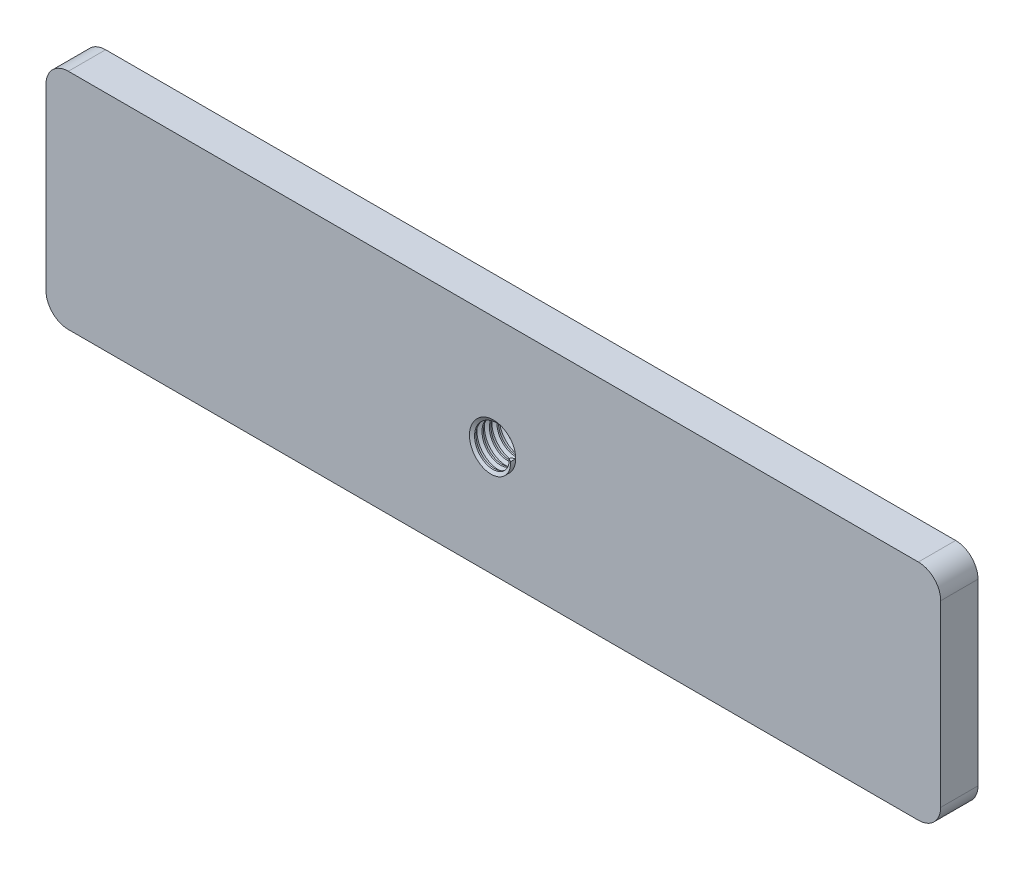
SolidWorks part; units mm, degrees
ref_plane "Front Plane" through (0, 0, 0) normal (0, 0, 1) x (1, 0, 0)
ref_plane "Top Plane" through (0, 0, 0) normal (0, 1, 0) x (1, 0, 0)
ref_plane "Right Plane" through (0, 0, 0) normal (1, 0, 0) x (0, 0, -1)
sketch "Sketch2" plane through (0, 0, 0) normal (0, 0, 1) x (1, 0, 0)
  line L1 (-57, -15) -> (57, -15)
  line L2 (-60, -12) -> (-60, 12)
  line L3 (-57, 15) -> (57, 15)
  line L4 (60, -12) -> (60, 12)
  line L5 (-60, -15) -> (60, 15) construction
  line L6 (-60, 15) -> (60, -15) construction
  circle A0 centre (0, 0) radius 3
  arc A1 (57, 15) -> (60, 12) centre (57, 12) cw
  arc A2 (57, -15) -> (60, -12) centre (57, -12) ccw
  arc A3 (-57, -15) -> (-60, -12) centre (-57, -12) cw
  arc A4 (-60, 12) -> (-57, 15) centre (-57, 12) cw
  point P0 (0, 0)
  dimension "D1" = 6
  dimension "D4" = 3
  dimension "D2" = 120
  dimension "D3" = 30
extrude "Boss-Extrude1" add sketch "Sketch2" along normal blind 5
thread "Thread1" pitch 0.8 method extrude profile "Thread Profile2" start angle 0, offset 0, length 0, pitch 1, diameter 6
ref_plane "Plane2" through (3, 0, 0) normal (0, -1, 0) x (1, 0, 0)
sketch "Thread Profile2" plane through (3, 0, 0) normal (0, -1, 0) x (1, 0, 0)
  line L0 (0, 0) -> (0, 0.8) construction
  line L11 (0, 0) -> (0, 0.7)
  line L12 (0, 0.7) -> (-0.433, 0.45)
  line L13 (-0.433, 0.45) -> (-0.433, 0.25)
  line L15 (-0.433, 0.25) -> (0, 0)
  line L17 (-0.433, 0.35) -> (0, 0.35) construction
  point P2 (0, 0)
  dimension "Pitch" = 0.8
  dimension "Profile_Angle" = 60
  dimension "Profile_Land" = 0.2
  dimension "Profile_Height" = 0.433
